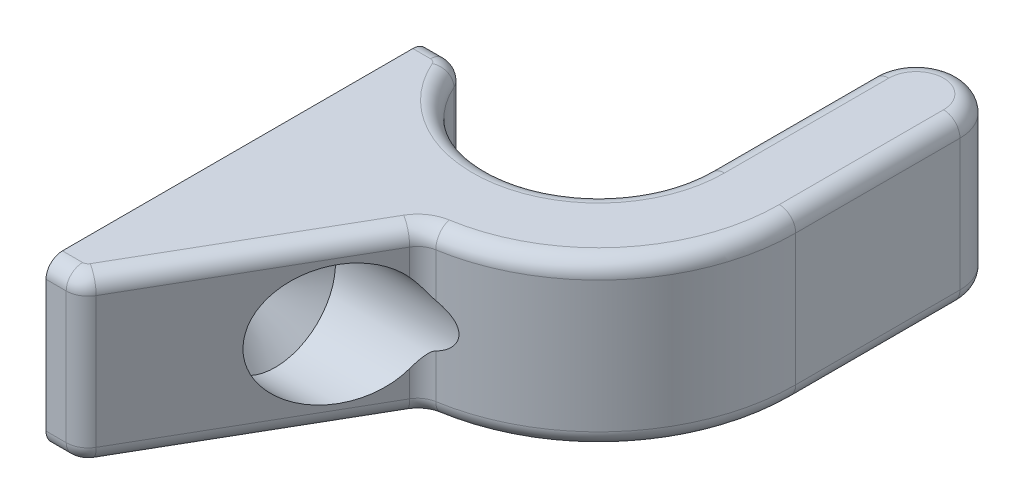
SolidWorks part; units mm, degrees
material "ABS"
ref_plane "Front" through (0, 0, 0) normal (0, 0, 1) x (1, 0, 0)
ref_plane "Top" through (0, 0, 0) normal (0, 1, 0) x (1, 0, 0)
ref_plane "Right" through (0, 0, 0) normal (1, 0, 0) x (0, 0, -1)
sketch "Esquisse1" plane through (0, 0, 0) normal (0, 1, 0) x (1, 0, 0)
  line L8 (3, -15) -> (0, -15)
  line L9 (0, 20) -> (0, -15)
  line L10 (14.547, 5) -> (3, -15)
  line L16 (30.5729, 22.8914) -> (30.5729, 37.8914)
  line L17 (22.5729, 37.8914) -> (22.5729, 22.8914)
  line L19 (3, 20) -> (0, 20)
  arc A0 (14.547, 5) -> (30.5729, 22.8914) centre (12.5729, 22.8914) ccw
  arc A1 (30.5729, 37.8914) -> (22.5729, 37.8914) centre (26.5729, 37.8914) ccw
  arc A2 (22.5729, 22.8914) -> (3, 20) centre (12.5729, 22.8914) cw
  dimension "D1" = 15
  dimension "D6" = 10
  dimension "D2" = 3
  dimension "D5" = 30
  dimension "D7" = 15
  dimension "D3" = 8
  dimension "D9" = 12.5729
  dimension "D4" = 5
  dimension "D8" = 20
extrude "Boss.-Extru.1" add sketch "Esquisse1" along normal mid plane 15
fillet "Congé1" radius 2 3 edges at (3, 0, -20) (14.547, 0, -5) (3, 0, 15)
sketch "Esquisse2" plane through (0, 0, 0) normal (-1, 0, 0) x (0, 0, 1)
  circle A0 centre (0, 0) radius 2
  dimension "D1" = 4
extrude "Enlèv. mat.-Extru.1" cut sketch "Esquisse2" against normal blind 3
sketch "Esquisse3" plane through (3, 0, 0) normal (-1, 0, 0) x (0, 0, 1)
  circle A0 centre (0, 0) radius 5.5
  dimension "D1" = 11
extrude "Enlèv. mat.-Extru.2" cut sketch "Esquisse3" against normal through all
chamfer "Chanfrein1" distance 3.5 angle 40 1 edges at (3, 0, 5.5) first distance on face at (3, 0, 2)
fillet "Congé2" radius 1.5 22 edges at (0.9226, -7.5, 15) (2.8453, -7.5, 14.7321) (8.8173, -7.5, 4.9241) (14.6528, -7.5, -4.7975) (26.2861, -7.5, -11.2318) (30.5729, -7.5, -30.3914) (26.5729, -7.5, -41.8914) (22.5729, -7.5, -30.3914) (0.8075, -7.5, -20) (2.7035, -7.5, -19.6779) (0.9226, 7.5, 15) (2.8453, 7.5, 14.7321) (8.8173, 7.5, 4.9241) (14.6528, 7.5, -4.7975) (26.2861, 7.5, -11.2318) (30.5729, 7.5, -30.3914) (26.5729, 7.5, -41.8914) (22.5729, 7.5, -30.3914) (0.8075, 7.5, -20) (2.7035, 7.5, -19.6779) (14.6567, -7.5, -13.1109) (14.6567, 7.5, -13.1109)
